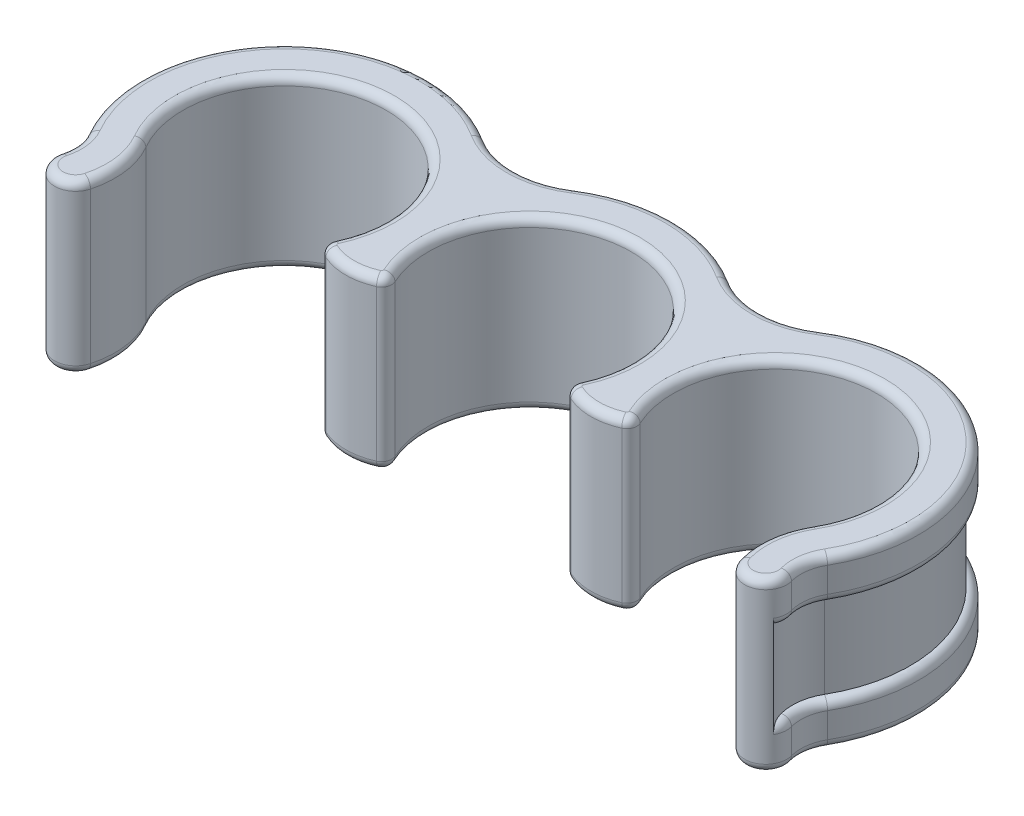
SolidWorks part; units mm, degrees
ref_plane "Front Plane" through (0, 0, 0) normal (0, 0, 1) x (1, 0, 0)
ref_plane "Top Plane" through (0, 0, 0) normal (0, 1, 0) x (1, 0, 0)
ref_plane "Right Plane" through (0, 0, 0) normal (1, 0, 0) x (0, 0, -1)
sketch "Sketch1" plane through (0, 0, 0) normal (0, 1, 0) x (1, 0, 0)
  line L0 (0, 0) -> (15249.8631, 0) construction
  line L1 (0, 0) -> (0, 15249.8631) construction
  line L2 (9.271, 0) -> (2.6169, -3.8417) construction
  line L3 (9.271, 0) -> (18.6747, -5.4293) construction
  line L4 (18.3576, -7.8385) -> (15.2907, -8.6603) construction
  line L6 (-9.271, 0) -> (-9.271, 50000) construction
  line L7 (-18.542, 0) -> (-18.542, 15249.8631) construction
  circle A0 centre (-9.271, 0) radius 7.6835 construction
  circle A1 centre (9.271, 0) radius 7.6835 construction
  arc A2 (15.9251, -3.8418) -> (2.2951, -3.2208) centre (9.271, 0) ccw
  arc A3 (-2.2951, -3.2208) -> (-16.9545, 0) centre (-9.271, 0) ccw
  arc A4 (-1.9177, -4.2343) -> (1.9177, -4.2343) centre (0, 0) ccw
  arc A5 (3.421, 9.1479) -> (18.6747, -5.4293) centre (9.271, 0) cw
  arc A6 (3.421, 9.1479) -> (-3.421, 9.1479) centre (0, 14.4976) cw
  arc A7 (-3.421, 9.1479) -> (-15.121, 9.1479) centre (-9.271, 0) ccw
  arc A11 (18.6747, -5.4293) -> (18.3576, -7.8385) centre (21.4244, -7.0168) ccw
  arc A12 (18.3576, -7.8385) -> (15.2907, -8.6603) centre (16.8241, -8.2494) cw
  arc A13 (15.2907, -8.6603) -> (15.9251, -3.8418) centre (21.4244, -7.0168) cw
  arc A14 (1.9177, -4.2343) -> (2.2951, -3.2208) centre (1.6033, -3.5402) ccw
  arc A15 (-1.9177, -4.2343) -> (-2.2951, -3.2208) centre (-1.6033, -3.5402) cw
  arc A16 (-16.6243, -4.2343) -> (-16.2469, -3.2208) centre (-16.9387, -3.5402) ccw
  arc A17 (-20.4597, -4.2343) -> (-20.8371, -3.2208) centre (-20.1453, -3.5402) cw
  arc A18 (-16.6243, -4.2343) -> (-20.4597, -4.2343) centre (-18.542, 0) cw
  arc A19 (-16.9545, 0) -> (-16.2469, -3.2208) centre (-9.271, 0) ccw
  arc A21 (-34.4671, -3.8418) -> (-20.8371, -3.2208) centre (-27.813, 0) cw
  arc A22 (-36.8996, -7.8385) -> (-33.8327, -8.6603) centre (-35.3661, -8.2494) ccw
  arc A23 (-33.8327, -8.6603) -> (-34.4671, -3.8418) centre (-39.9664, -7.0168) ccw
  arc A24 (-37.2167, -5.4293) -> (-36.8996, -7.8385) centre (-39.9664, -7.0168) cw
  arc A25 (-21.963, 9.1479) -> (-37.2167, -5.4293) centre (-27.813, 0) ccw
  arc A26 (-21.963, 9.1479) -> (-15.121, 9.1479) centre (-18.542, 14.4976) ccw
  point P7 (-1.5875, 0)
  point P10 (1.5875, 0)
  point P38 (-27.555, 0)
  point P44 (0, 0)
  point P53 (-24.4418, 0)
  point P54 (-24.1222, 0)
  dimension "D1" = 15.367
  dimension "D3" = 30
  dimension "D4" = 30
  dimension "D5" = 0.762
  dimension "D6" = 3.175
  dimension "D7" = 1.5875
  dimension "D9" = 6.35
  dimension "D10" = 45
  dimension "D8" = 6.35
  dimension "D2" = 3.175
extrude "Boss-Extrude1" add sketch "Sketch1" along normal mid plane 12.7
fillet "Fillet1" radius 0.635 40 edges at (18.2765, -6.35, 6.6023) (17.235, -6.35, 9.7828) (15.1287, -6.35, 6.1879) (9.6207, -6.35, -7.6755) (2.3174, -6.35, 3.8061) (0, -6.35, 4.6484) (-2.3174, -6.35, 3.8061) (-9.271, -6.35, -7.6835) (-9.271, -6.35, -10.8585) (0, -6.35, -8.1476) (18.2765, 6.35, 6.6023) (17.235, 6.35, 9.7828) (15.1287, 6.35, 6.1879) (9.6207, 6.35, -7.6755) (2.3174, 6.35, 3.8061) (0, 6.35, 4.6484) (-2.3174, 6.35, 3.8061) (-9.271, 6.35, -7.6835) (-9.271, 6.35, -10.8585) (0, 6.35, -8.1476) (16.7731, -6.35, -7.8502) (16.7731, 6.35, -7.8502) (-16.2246, -6.35, 3.8061) (-18.542, -6.35, 4.6484) (-20.8594, -6.35, 3.8061) (-28.1627, -6.35, -7.6755) (-33.6707, -6.35, 6.1879) (-35.777, -6.35, 9.7828) (-36.8185, -6.35, 6.6023) (-35.3151, -6.35, -7.8502) (-18.542, -6.35, -8.1476) (-16.2246, 6.35, 3.8061) (-18.542, 6.35, 4.6484) (-20.8594, 6.35, 3.8061) (-28.1627, 6.35, -7.6755) (-33.6707, 6.35, 6.1879) (-35.777, 6.35, 9.7828) (-36.8185, 6.35, 6.6023) (-35.3151, 6.35, -7.8502) (-18.542, 6.35, -8.1476)
sketch "Sketch2" plane through (0, 0, 0) normal (0, 1, 0) x (1, 0, 0)
  arc A9 (-22.3051, 8.613) -> (-36.6668, -5.1118) centre (-27.813, 0) ccw construction
  arc A10 (-36.2862, -8.0029) -> (-36.6668, -5.1118) centre (-39.9664, -7.0168) ccw construction
  arc A11 (-22.3051, 8.613) -> (-14.7789, 8.613) centre (-18.542, 14.4976) ccw construction
  arc A12 (-3.7631, 8.613) -> (-14.7789, 8.613) centre (-9.271, 0) ccw construction
  arc A13 (-3.7631, 8.613) -> (3.7631, 8.613) centre (0, 14.4976) ccw construction
  arc A14 (18.1248, -5.1118) -> (17.7442, -8.0029) centre (21.4244, -7.0168) ccw construction
  arc A15 (18.1248, -5.1118) -> (3.7631, 8.613) centre (9.271, 0) ccw construction
  arc A16 (18.1248, -5.1118) -> (18.1985, -9.044) centre (21.4244, -7.0168) ccw
  arc A17 (18.1248, -5.1118) -> (3.7631, 8.613) centre (9.271, 0) ccw
  arc A18 (-3.7631, 8.613) -> (3.7631, 8.613) centre (0, 14.4976) ccw
  arc A19 (-3.7631, 8.613) -> (-14.7789, 8.613) centre (-9.271, 0) ccw
  arc A20 (-22.3051, 8.613) -> (-14.7789, 8.613) centre (-18.542, 14.4976) ccw
  arc A21 (-36.7405, -9.044) -> (-36.6668, -5.1118) centre (-39.9664, -7.0168) ccw
  arc A22 (-22.3051, 8.613) -> (-36.6668, -5.1118) centre (-27.813, 0) ccw
  arc A44 (-3.421, 9.1479) -> (-15.121, 9.1479) centre (-9.271, 0) ccw
  arc A45 (-3.421, 9.1479) -> (3.421, 9.1479) centre (0, 14.4976) ccw
  arc A46 (18.6747, -5.4293) -> (3.421, 9.1479) centre (9.271, 0) ccw
  arc A47 (18.6747, -5.4293) -> (18.3576, -7.8385) centre (21.4244, -7.0168) ccw
  arc A48 (15.2907, -8.6603) -> (18.3576, -7.8385) centre (16.8241, -8.2494) ccw
  arc A49 (15.9251, -3.8418) -> (15.2907, -8.6603) centre (21.4244, -7.0168) ccw
  arc A50 (15.9251, -3.8418) -> (2.2951, -3.2208) centre (9.271, 0) ccw
  arc A51 (1.9177, -4.2343) -> (2.2951, -3.2208) centre (1.6033, -3.5402) ccw
  arc A52 (-1.9177, -4.2343) -> (1.9177, -4.2343) centre (0, 0) ccw
  arc A53 (-2.2951, -3.2208) -> (-1.9177, -4.2343) centre (-1.6033, -3.5402) ccw
  arc A54 (-2.2951, -3.2208) -> (-16.9545, 0) centre (-9.271, 0) ccw
  arc A55 (-16.9545, 0) -> (-16.2469, -3.2208) centre (-9.271, 0) ccw
  arc A56 (-16.6243, -4.2343) -> (-16.2469, -3.2208) centre (-16.9387, -3.5402) ccw
  arc A57 (-20.4597, -4.2343) -> (-16.6243, -4.2343) centre (-18.542, 0) ccw
  arc A58 (-20.8371, -3.2208) -> (-20.4597, -4.2343) centre (-20.1453, -3.5402) ccw
  arc A59 (-20.8371, -3.2208) -> (-34.4671, -3.8418) centre (-27.813, 0) ccw
  arc A60 (-33.8327, -8.6603) -> (-34.4671, -3.8418) centre (-39.9664, -7.0168) ccw
  arc A61 (-36.8996, -7.8385) -> (-33.8327, -8.6603) centre (-35.3661, -8.2494) ccw
  arc A62 (-36.8996, -7.8385) -> (-37.2167, -5.4293) centre (-39.9664, -7.0168) ccw
  arc A63 (-21.963, 9.1479) -> (-37.2167, -5.4293) centre (-27.813, 0) ccw
  arc A64 (-21.963, 9.1479) -> (-15.121, 9.1479) centre (-18.542, 14.4976) ccw
  arc A65 (-3.421, 9.1479) -> (-15.121, 9.1479) centre (-9.271, 0) ccw
  arc A66 (-3.421, 9.1479) -> (3.421, 9.1479) centre (0, 14.4976) ccw
  arc A67 (18.6747, -5.4293) -> (3.421, 9.1479) centre (9.271, 0) ccw
  arc A68 (18.6747, -5.4293) -> (18.3576, -7.8385) centre (21.4244, -7.0168) ccw
  arc A69 (18.1985, -9.044) -> (18.3576, -7.8385) centre (16.8241, -8.2494) ccw
  arc A82 (-36.8996, -7.8385) -> (-36.7405, -9.044) centre (-35.3661, -8.2494) ccw
  arc A83 (-36.8996, -7.8385) -> (-37.2167, -5.4293) centre (-39.9664, -7.0168) ccw
  arc A84 (-21.963, 9.1479) -> (-37.2167, -5.4293) centre (-27.813, 0) ccw
  arc A85 (-21.963, 9.1479) -> (-15.121, 9.1479) centre (-18.542, 14.4976) ccw
  dimension "D1" = 0
extrude "Cut-Extrude1" cut sketch "Sketch2" against normal mid plane 6.35
fillet "Fillet2" radius 0.635 18 edges at (18.398, 3.175, 8.4571) (18.2765, 3.175, 6.6023) (-9.271, 3.175, -10.8585) (0, 3.175, -8.1476) (18.398, -3.175, 8.4571) (18.2765, -3.175, 6.6023) (-9.271, -3.175, -10.8585) (0, -3.175, -8.1476) (16.7731, 3.175, -7.8502) (16.7731, -3.175, -7.8502) (-36.94, 3.175, 8.4571) (-36.8185, 3.175, 6.6023) (-35.3151, 3.175, -7.8502) (-18.542, 3.175, -8.1476) (-36.94, -3.175, 8.4571) (-36.8185, -3.175, 6.6023) (-35.3151, -3.175, -7.8502) (-18.542, -3.175, -8.1476)
